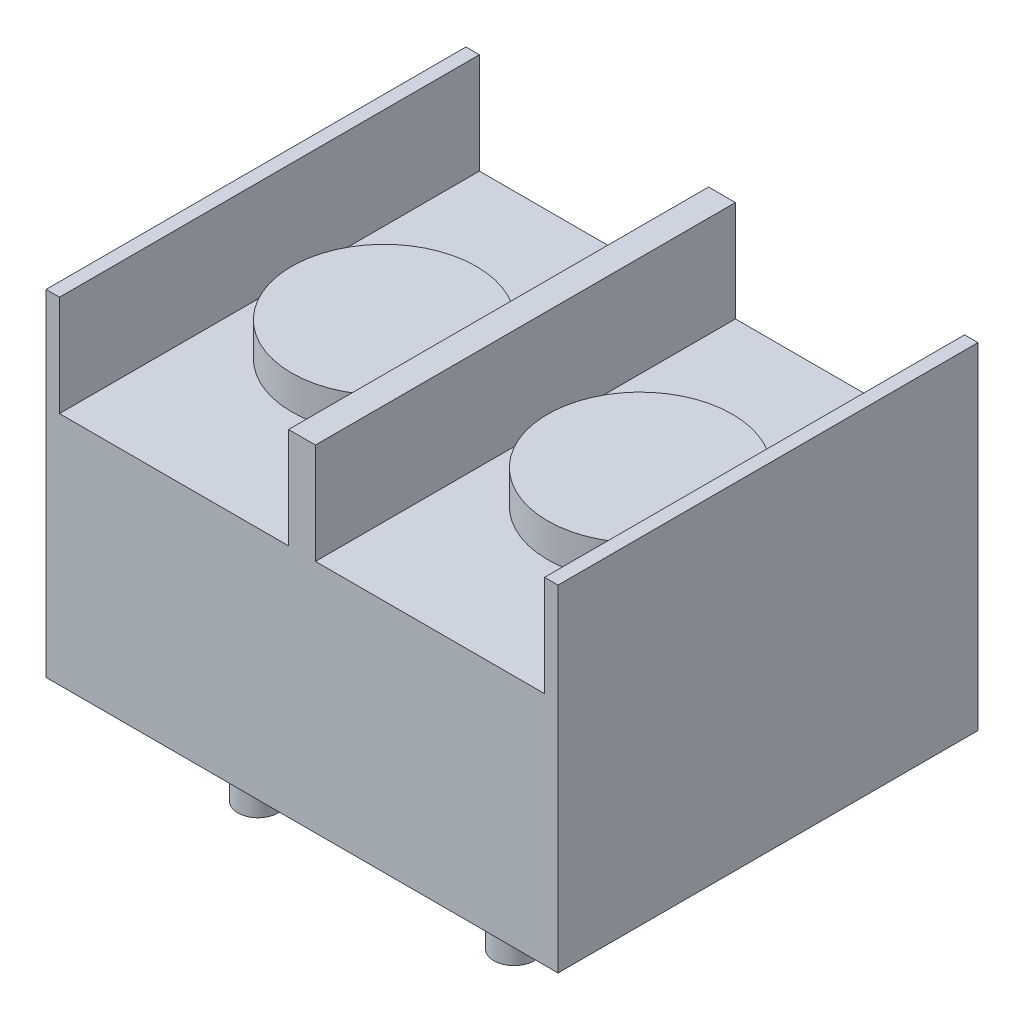
SolidWorks part; units mm, degrees
ref_plane "前视基准面" through (0, 0, 0) normal (0, 0, 1) x (1, 0, 0)
ref_plane "上视基准面" through (0, 0, 0) normal (0, 1, 0) x (1, 0, 0)
ref_plane "右视基准面" through (0, 0, 0) normal (1, 0, 0) x (0, 0, -1)
sketch "草图1" plane through (0, 0, 0) normal (0, 1, 0) x (1, 0, 0)
  line L0 (-11.1447, 0) -> (12.1543, 0) construction
  line L1 (-7.62, 6.25) -> (7.62, 6.25)
  line L2 (-7.62, 6.25) -> (-7.62, -6.25)
  line L3 (-7.62, -6.25) -> (7.62, -6.25)
  line L4 (7.62, 6.25) -> (7.62, -6.25)
  line L5 (0, 11.4931) -> (0, -8.9219) construction
  dimension "D1" = 15.24
  dimension "D2" = 12.5
extrude "拉伸1" add sketch "草图1" along normal blind 10
sketch "草图2" plane through (0, 10, 0) normal (0, 1, 0) x (-1, 0, 0)
  line L0 (0, 8.3959) -> (0, -7.6637) construction
  line L2 (-7.62, -6.25) -> (7.62, -6.25) construction
  line L3 (7.22, -6.25) -> (0.4, -6.25)
  line L4 (7.22, -6.25) -> (7.22, 6.25)
  line L5 (7.22, 6.25) -> (0.4, 6.25)
  line L7 (0.4, -6.25) -> (0.4, 6.25)
  line L8 (7.62, 6.25) -> (-7.62, 6.25) construction
  line L9 (7.62, -6.25) -> (7.62, 6.25) construction
  line L10 (-0.4, -6.25) -> (-0.4, 6.25)
  line L11 (-7.22, 6.25) -> (-0.4, 6.25)
  line L12 (-7.22, -6.25) -> (-7.22, 6.25)
  line L13 (-7.22, -6.25) -> (-0.4, -6.25)
  dimension "D1" = 0.4
  dimension "D2" = 0.4
extrude "切除-拉伸1" cut sketch "草图2" against normal blind 3
sketch "草图3" plane through (0, 0, 0) normal (0, -1, 0) x (1, 0, 0)
  line L0 (9.9189, 3.75) -> (-9.4712, 3.75) construction
  line L1 (0, -8.128) -> (0, 7.9902) construction
  circle A0 centre (3.81, 3.75) radius 0.6
  circle A1 centre (-3.81, 3.75) radius 0.6
  dimension "D2" = 1.2
  dimension "D1" = 10
  dimension "D3" = 3.81
extrude "拉伸2" add sketch "草图3" along normal blind 2.54
sketch "草图4" plane through (0, 7, 0) normal (0, 1, 0) x (-1, 0, 0)
  line L0 (-9.5136, 0) -> (8.6579, 0) construction
  line L1 (0, -7.7686) -> (0, 8.3952) construction
  circle A0 centre (-3.81, 0) radius 2.75
  circle A1 centre (3.81, 0) radius 2.75
  dimension "D1" = 5.5
  dimension "D2" = 3.81
extrude "拉伸3" add sketch "草图4" along normal blind 1
